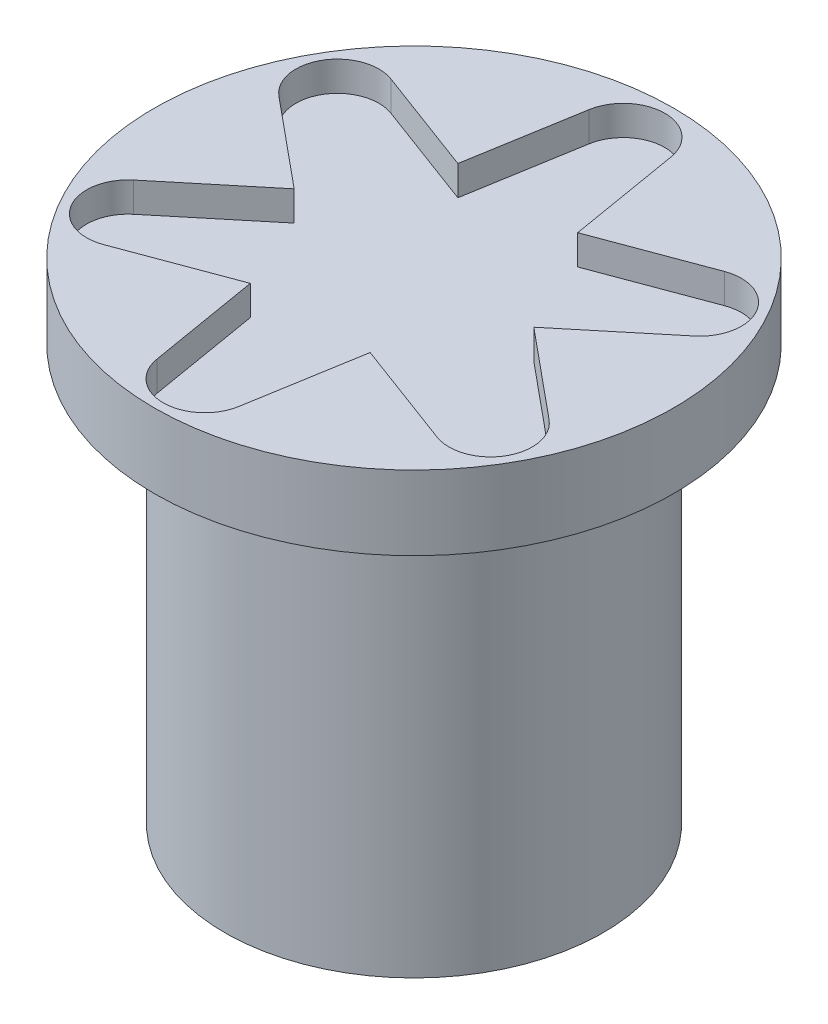
SolidWorks part; units mm, degrees
material "PBT General Purpose"
ref_plane "Front Plane" through (0, 0, 0) normal (0, 0, 1) x (1, 0, 0)
ref_plane "Top Plane" through (0, 0, 0) normal (0, 1, 0) x (1, 0, 0)
ref_plane "Right Plane" through (0, 0, 0) normal (1, 0, 0) x (0, 0, -1)
sketch "Sketch1" plane through (0, 0, 0) normal (0, 1, 0) x (1, 0, 0)
  line L0 (4, 12.1063) -> (4, 7.7822)
  line L1 (-3.75, -3.75) -> (3.75, -3.75)
  line L2 (-3.75, -3.75) -> (-3.75, 3.75)
  line L3 (-3.75, 3.75) -> (3.75, 3.75)
  line L4 (3.75, -3.75) -> (3.75, 3.75)
  line L5 (-3.75, -3.75) -> (3.75, 3.75) construction
  line L6 (-3.75, 3.75) -> (3.75, -3.75) construction
  line L12 (-12.1063, -4) -> (-7.7822, -4)
  arc A0 (-12.1063, -4) -> (4, 12.1063) centre (0, 0) ccw
  arc A2 (4, 7.7822) -> (-7.7822, -4) centre (0, 0) ccw
  point P0 (0, 0)
  dimension "D3" = 25.5
  dimension "D4" = 17.5
  dimension "D1" = 7.5
  dimension "D2" = 7.5
  dimension "D5" = 4
  dimension "D6" = 4
extrude "Boss-Extrude1" add sketch "Sketch1" against normal blind 3
sketch "Sketch2" plane through (0, 0, 0) normal (0, 1, 0) x (1, 0, 0)
  line L0 (-7.7822, -4) -> (-12.1063, -4) construction
  line L1 (-8.8917, -4) -> (-12.1063, -4)
  line L2 (4, 12.1063) -> (4, 7.7822) construction
  line L3 (4, 12.1063) -> (4, 8.8917)
  arc A0 (-8.8917, -4) -> (4, 8.8917) centre (0, 0) ccw
  arc A1 (-12.1063, -4) -> (4, 12.1063) centre (0, 0) ccw construction
  arc A2 (-12.1063, -4) -> (4, 12.1063) centre (0, 0) ccw
  dimension "D1" = 19.5
extrude "Boss-Extrude2" add sketch "Sketch2" along normal blind 25
sketch "Sketch3" plane through (0, 25, 0) normal (0, 1, 0) x (1, 0, 0)
  circle A0 centre (0, 0) radius 17.5
  dimension "D1" = 35
extrude "Boss-Extrude3" add sketch "Sketch3" along normal blind 5
sketch "Sketch4" plane through (0, 30, 0) normal (0, 1, 0) x (1, 0, 0)
  line L0 (-2.7611, 14.5654) -> (-4.0973, 6.6372)
  line L1 (2.7611, 14.5654) -> (4.0973, 6.6372)
  arc A0 (-4.0973, 6.6372) -> (4.0973, 6.6372) centre (0, 0) ccw
  arc A1 (2.7611, 14.5654) -> (-2.7611, 14.5654) centre (0, 14.1) ccw
  dimension "D1" = 15.6
  dimension "D2" = 5.6
  dimension "D3" = 14.1
  dimension "D4" = 8.04
  dimension "D5" = 8.04
extrude "Cut-Extrude1" cut sketch "Sketch4" against normal blind 2
pattern_circular "CirPattern1" count 6 over 360 about axis through (0, 28, 0) along (0, 1, 0) of "Cut-Extrude1"
